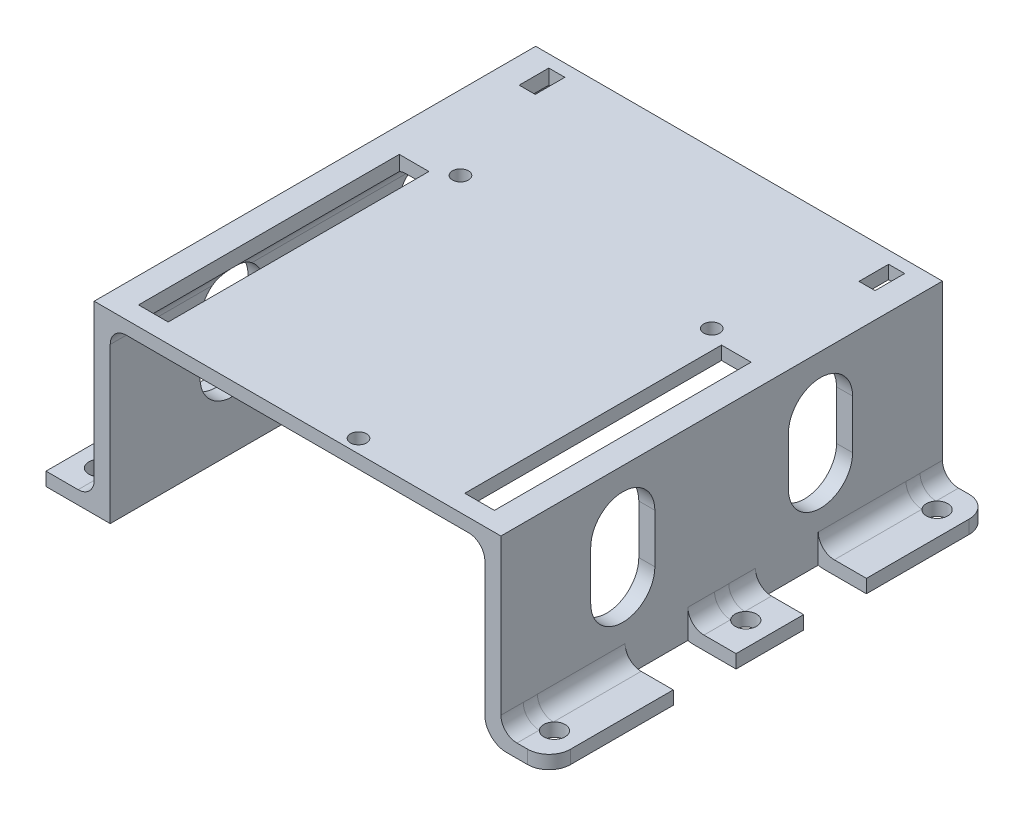
SolidWorks part; units mm, degrees
ref_plane "Front Plane" through (0, 0, 0) normal (0, 0, 1) x (1, 0, 0)
ref_plane "Top Plane" through (0, 0, 0) normal (0, 1, 0) x (1, 0, 0)
ref_plane "Right Plane" through (0, 0, 0) normal (1, 0, 0) x (0, 0, -1)
sketch "Sketch1" plane through (0, 0, 0) normal (0, 1, 0) x (1, 0, 0)
  line L0 (-35, 41.25) -> (-38, 41.25)
  line L1 (-35, -41.25) -> (35, -41.25)
  line L2 (-35, -41.25) -> (-35, 41.25)
  line L3 (-35, 41.25) -> (35, 41.25)
  line L4 (35, -41.25) -> (35, 41.25)
  line L5 (-35, -41.25) -> (35, 41.25) construction
  line L6 (-35, 41.25) -> (35, -41.25) construction
  line L7 (-38, 41.25) -> (-38, -41.25)
  line L8 (-38, -41.25) -> (-35, -41.25)
  line L9 (-38, -41.25) -> (-47, -41.25)
  line L10 (-47, -41.25) -> (-47, 41.25)
  line L11 (-47, 41.25) -> (-38, 41.25)
  line L12 (0, 21.0903) -> (0, -28.1695) construction
  line L13 (47, 41.25) -> (38, 41.25)
  line L14 (47, -41.25) -> (47, 41.25)
  line L15 (38, -41.25) -> (47, -41.25)
  line L16 (38, 41.25) -> (38, -41.25)
  line L17 (38, -41.25) -> (35, -41.25)
  line L18 (35, 41.25) -> (38, 41.25)
  line L19 (-42.5, 41.25) -> (-42.5, -41.25) construction
  line L20 (42.5, 41.25) -> (42.5, -41.25) construction
  line L21 (-58.5063, 0) -> (72.588, 0) construction
  circle A0 centre (-42.5, 35.75) radius 2
  circle A1 centre (-42.5, -35.75) radius 2
  circle A2 centre (42.5, -35.75) radius 2
  circle A3 centre (42.5, 35.75) radius 2
  circle A4 centre (-42.5, 0) radius 2
  circle A5 centre (42.5, 0) radius 2
  point P0 (0, 0)
  dimension "D3" = 4
  dimension "D4" = 4
  dimension "D5" = 5.5
  dimension "D9" = 4
  dimension "D10" = 4
  dimension "D1" = 3
  dimension "D2" = 9
  dimension "D6" = 5.5
  dimension "D7" = 82.5
  dimension "D8" = 70
extrude "Boss-Extrude1" add sketch "Sketch1" along normal blind 2.5 contours L11 L10 L9 L7 A1 A0 | L13 L16 L15 L14 A2 A3 region at (-38.8299, 0, 0) region at (42.5, 0, -40.4201)
extrude "Boss-Extrude2" add sketch "Sketch1<3>" along normal blind 32 contours L7 L8 L2 L0 | L18 L4 L17 L16 region at (-36.5, 0, 0) region at (36.5, 0, 0)
sketch "Sketch1<3>" plane through (0, 0, 0) normal (0, 1, 0) x (1, 0, 0) same geometry as "Sketch1"
extrude "Boss-Extrude3" add sketch "Sketch1<5>" along normal blind 2.5 from surface contours L7 L8 L2 L0 | L18 L4 L17 L16 | L1 L4 L3 L2 region at (-36.5, 0, 0) region at (0, 0, 0) region at (36.5, 0, 0) starting at face at (-36.5, 32, 0)
sketch "Sketch1<5>" plane through (0, 0, 0) normal (0, 1, 0) x (1, 0, 0) same geometry as "Sketch1"
fillet "Fillet1" radius 3 2 edges at (35, 32, 0) (-35, 32, 0)
fillet "Fillet2" radius 4 2 edges at (47, 1.25, 41.25) (47, 1.25, -41.25)
sketch "Sketch2" plane through (0, 2.5, 0) normal (0, 1, 0) x (1, 0, 0)
  line L0 (-42.5, 0) -> (42.5, 0) construction
  line L1 (48.0101, 18.0465) -> (38, 18.0465)
  line L2 (38, -41.25) -> (38, 41.25) construction
  line L3 (38, 18.0465) -> (38, 6.3106)
  line L4 (38, 6.3106) -> (48.0101, 6.3106)
  line L5 (48.0101, 6.3106) -> (48.0101, 18.0465)
  line L6 (48.0101, -6.3106) -> (48.0101, -18.0465)
  line L7 (38, -6.3106) -> (48.0101, -6.3106)
  line L8 (38, -18.0465) -> (38, -6.3106)
  line L9 (48.0101, -18.0465) -> (38, -18.0465)
extrude "Cut-Extrude1" cut sketch "Sketch2" against normal through all both and the other way through all
fillet "Fillet3" radius 4 1 edges at (35, 0, 0)
fillet "Fillet4" radius 3 4 edges at (-38, 2.5, 0) (38, 2.5, 29.6482) (38, 2.5, 0) (38, 2.5, -29.6482)
sketch "Sketch3" plane through (-38, 0, 0) normal (-1, 0, 0) x (0, 0, 1)
  line L0 (18.4733, 15.128) -> (18.4733, 24.2824) construction
  line L1 (12.4833, 15.128) -> (12.4833, 24.2824)
  line L2 (24.4633, 15.128) -> (24.4633, 24.2824)
  line L3 (0, 7.6501) -> (0, 29.8023) construction
  line L4 (-18.4733, 15.128) -> (-18.4733, 24.2824) construction
  line L5 (-12.4833, 15.128) -> (-12.4833, 24.2824)
  line L6 (-24.4633, 15.128) -> (-24.4633, 24.2824)
  arc A0 (12.4833, 15.128) -> (24.4633, 15.128) centre (18.4733, 15.128) ccw
  arc A1 (24.4633, 24.2824) -> (12.4833, 24.2824) centre (18.4733, 24.2824) ccw
  arc A2 (-12.4833, 15.128) -> (-24.4633, 15.128) centre (-18.4733, 15.128) cw
  arc A3 (-24.4633, 24.2824) -> (-12.4833, 24.2824) centre (-18.4733, 24.2824) cw
  point P2 (18.4733, 19.7052)
  point P12 (-18.4733, 19.7052)
  point P17 (0, 0)
  point P18 (24.4633, 15.128)
extrude "Cut-Extrude2" cut sketch "Sketch3" against normal through all both and the other way through all
sketch "Sketch4" plane through (0, 34.5, 0) normal (0, 1, 0) x (1, 0, 0)
  line L0 (-38, -41.25) -> (-38, 41.25) construction
  line L1 (38, -41.25) -> (-38, -41.25) construction
  line L2 (-31.75, -36.21) -> (-29.21, -36.21) construction
  line L3 (-31.75, -36.21) -> (-31.75, 9.51) construction
  line L4 (-31.75, 9.51) -> (-29.21, 9.51) construction
  line L5 (-29.21, -36.21) -> (-29.21, 9.51) construction
  line L6 (29.21, -36.21) -> (31.75, -36.21) construction
  line L7 (29.21, -36.21) -> (29.21, 9.51) construction
  line L8 (29.21, 9.51) -> (31.75, 9.51) construction
  line L9 (31.75, -36.21) -> (31.75, 9.51) construction
  line L10 (-31.75, 34.91) -> (-31.75, 37.45) construction
  line L11 (-33.25, -37.71) -> (-27.71, -37.71)
  line L12 (-33.25, -37.71) -> (-33.25, 11.01)
  line L13 (-33.25, 11.01) -> (-27.71, 11.01)
  line L14 (-27.71, -37.71) -> (-27.71, 11.01)
  line L15 (27.71, -37.71) -> (33.25, -37.71)
  line L16 (27.71, -37.71) -> (27.71, 10.26)
  line L17 (27.71, 10.26) -> (33.25, 10.26)
  line L18 (33.25, -37.71) -> (33.25, 10.26)
  line L19 (31.75, 34.91) -> (31.75, 37.45) construction
  line L21 (-31.75, 37.45) -> (31.75, 37.45) construction
  line L23 (-33.25, 33.41) -> (-30.25, 33.41)
  line L24 (-33.25, 33.41) -> (-33.25, 38.95)
  line L25 (-33.25, 38.95) -> (-30.25, 38.95)
  line L26 (-30.25, 33.41) -> (-30.25, 38.95)
  line L27 (30.25, 33.41) -> (33.25, 33.41)
  line L28 (30.25, 33.41) -> (30.25, 38.95)
  line L29 (30.25, 38.95) -> (33.25, 38.95)
  line L30 (33.25, 33.41) -> (33.25, 38.95)
  circle A0 centre (-24.13, 13.32) radius 1.5
  circle A1 centre (24.13, 12.03) radius 1.5
  circle A2 centre (8.89, -38.75) radius 1.5
  point P30 (-30.48, -36.21)
  dimension "D1" = 3
  dimension "D2" = 2.54
  dimension "D3" = 3
  dimension "D4" = 3
  dimension "D5" = 46.89
  dimension "D6" = 5.04
  dimension "D7" = 2.54
  dimension "D8" = 2.54
  dimension "D9" = 45.72
  dimension "D10" = 3.81
  dimension "D11" = 7.62
  dimension "D12" = 48.26
  dimension "D13" = 63.5
  dimension "D14" = 6.25
  dimension "D15" = 48.24
  dimension "D16" = 1.5
  dimension "D17" = 1.5
  dimension "D18" = 1.5
  dimension "D19" = 1.5
  dimension "D20" = 1.5
  dimension "D21" = 1.5
  dimension "D22" = 1.5
  dimension "D23" = 1.5
  dimension "D24" = 2.54
  dimension "D25" = 71.12
  dimension "D26" = 1.5
  dimension "D27" = 1.5
  dimension "D28" = 1.5
  dimension "D29" = 1.5
  dimension "D30" = 1.5
  dimension "D31" = 1.5
  dimension "D32" = 1.5
  dimension "D33" = 1.5
extrude "Cut-Extrude3" cut sketch "Sketch4" against normal through all both and the other way through all
